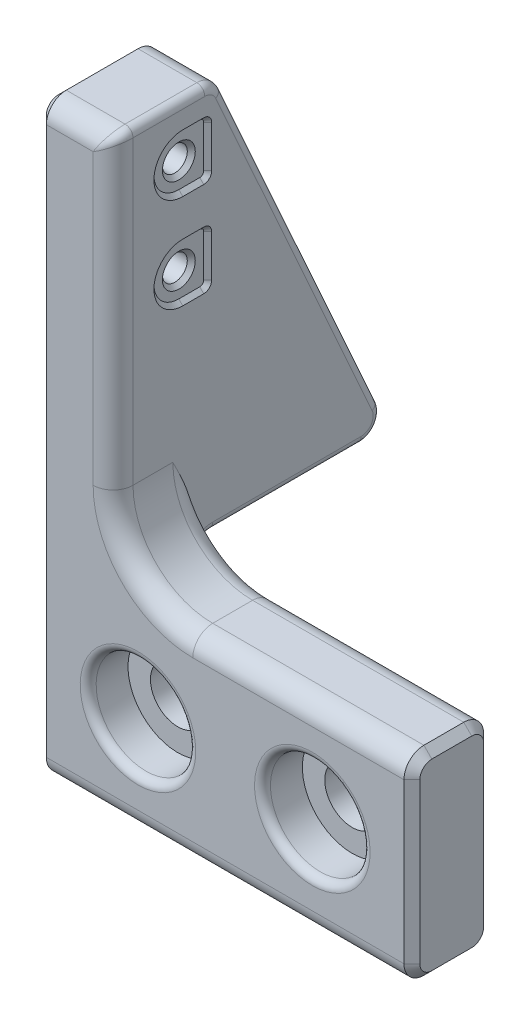
SolidWorks part; units mm, degrees
ref_plane "Front Plane" through (0, 0, 0) normal (0, 0, 1) x (1, 0, 0)
ref_plane "Top Plane" through (0, 0, 0) normal (0, 1, 0) x (1, 0, 0)
ref_plane "Right Plane" through (0, 0, 0) normal (1, 0, 0) x (0, 0, -1)
sketch "Sketch1" plane through (0, 0, 0) normal (1, 0, 0) x (0, 0, -1)
  line L6 (0, 0) -> (0, 20)
  line L7 (0, 20) -> (20, 20)
  line L8 (20, 20) -> (2.5, 59)
  line L9 (2.5, 59) -> (-8, 59)
  line L10 (-8, 59) -> (-8, 0)
  line L11 (-8, 0) -> (0, 0)
  dimension "D1" = 8
  dimension "D2" = 20
  dimension "D3" = 59
  dimension "D4" = 10.5
extrude "Boss-Extrude1" add sketch "Sketch1" against normal blind 7.5 contours L8 L9 L10 L11 L6 L7
sketch "Sketch2" plane through (0, 0, 0) normal (-1, 0, 0) x (0, 0, 1)
  line L0 (8, 59) -> (8, 0) construction
  line L1 (0, 0) -> (8, 0)
  line L2 (0, 0) -> (0, 20)
  line L3 (0, 20) -> (8, 20)
  line L4 (8, 0) -> (8, 20)
  line L5 (0, 20) -> (-20, 20) construction
extrude "Boss-Extrude2" add sketch "Sketch2" against normal blind 30
hole_wizard "CBORE for M5 SHCS1" positions "Sketch3" profile "Sketch4" counterbore size "M5" standard "ANSI Metric" end condition through all
sketch "Sketch3" plane through (0, 0, 8) normal (0, 0, 1) x (1, 0, 0)
  line L0 (30, 10) -> (20, 10) construction
  line L1 (30, 0) -> (30, 20) construction
  line L2 (20, 10) -> (2.5, 10) construction
  line L4 (30, 0) -> (30, 20) construction
  line L5 (-7.5, 59) -> (-7.5, 0) construction
  point P0 (2.5, 10)
  point P2 (20, 10)
  dimension "D1" = 10
  dimension "D2" = 10
sketch "Sketch4" plane through (2.5, 10, 8) normal (1, 0, 0) x (0, -1, 0)
  line L0 (0, 0) -> (0, 28)
  line L1 (0, 28) -> (2.75, 28)
  line L3 (2.75, 28) -> (2.75, 4)
  line L4 (2.75, 4) -> (5, 4)
  line L5 (5, 4) -> (5, 0)
  line L7 (5, 0) -> (0, 0)
  line L11 (0, -6.35) -> (0, 107.95) construction
  dimension "Thru Hole Dia." = 5.5
  dimension "Thru Hole Depth" = 28
  dimension "C'Bore Dia." = 10
  dimension "C'Bore Depth" = 4
sketch "Sketch5" plane through (0, 0, 0) normal (1, 0, 0) x (0, 0, -1)
  line L0 (-1, 44) -> (-1, 53.5) construction
  line L1 (-8, 59) -> (-8, 20) construction
  line L3 (2.5, 59) -> (-8, 59) construction
  circle A0 centre (-1, 53.5) radius 1.25
  circle A1 centre (-1, 44) radius 1.25
  dimension "D1" = 2.5
  dimension "D4" = 5.5
  dimension "D2" = 9.5
  dimension "D3" = 7
extrude "Cut-Extrude1" cut sketch "Sketch5" against normal through all
sketch "Sketch7" plane through (0, 0, 0) normal (1, 0, 0) x (0, 0, -1)
  line L0 (-1, 56) -> (1.5, 56)
  line L1 (1.5, 56) -> (1.5, 51)
  line L2 (1.5, 51) -> (-1, 51)
  line L3 (-1, 46.5) -> (1.5, 46.5)
  line L4 (1.5, 46.5) -> (1.5, 41.5)
  line L5 (1.5, 41.5) -> (-1, 41.5)
  arc A0 (-1, 46.5) -> (-1, 41.5) centre (-1, 44) ccw
  arc A1 (-1, 56) -> (-1, 51) centre (-1, 53.5) ccw
  dimension "D1" = 5
extrude "Cut-Extrude2" cut sketch "Sketch7" against normal blind 0.4
fillet "Fillet5" radius 8 1 edges at (0, 20, 4)
fillet "Fillet1" radius 2 9 edges at (19, 20, 8) (11.25, 0, 8) (11.25, 0, 0) (-3.75, 59, 8) (-3.75, 59, -2.5) (-3.75, 20, -20) (-3.75, 20, 0) (0, 43.5, 8) (2.3431, 22.3431, 8)
fillet "Fillet2" radius 2 2 edges at (19, 20, 0) (2.3431, 22.3431, 0)
chamfer "Chamfer1" distance 0.8 angle 45 22 edges at (30, 19.4142, 7.4142) (30, 10, 8) (30, 0.5858, 7.4142) (30, 0, 4) (30, 0.5858, 0.5858) (30, 10, 0) (30, 19.4142, 0.5858) (30, 20, 4) (-7.5, 44, -0.25) (-7.5, 53.5, -0.25) (-7.5, 0.5858, 0.5858) (-7.5, 10, 0) (-7.5, 19.4142, -0.5858) (-7.5, 20, -9.4552) (-7.5, 20.9132, -18.5894) (-7.5, 40.3188, -10.8826) (-7.5, 58.6789, -2.2922) (-7.5, 59, 2.3973) (-7.5, 58.4142, 7.4142) (-7.5, 29.5, 8) (-7.5, 0.5858, 7.4142) (-7.5, 0, 4)
fillet "Fillet3" radius 0.8 7 edges at (0, 19.4142, -0.5858) (0, 20, -9.4552) (0, 20.9132, -18.5894) (0, 40.3188, -10.8826) (0, 58.6789, -2.2922) (0, 59, 2.3973) (-0.5858, 58.4142, 7.4142)
fillet "Fillet4" radius 0.8 2 edges at (25, 10, 8) (7.5, 10, 8)
fillet "Fillet6" radius 0.4 4 edges at (-0.2, 51, -1.5) (-0.2, 41.5, -1.5) (-0.2, 46.5, -1.5) (-0.2, 56, -1.5)
chamfer "Chamfer2" distance 0.4 angle 45 14 edges at (0, 53.5, 3.5) (0, 44, 3.5) (-0.4, 44, -0.25) (-0.4, 53.5, -0.25) (0, 56, -0.05) (0, 51, -0.05) (0, 46.5, -0.05) (0, 41.5, -0.05) (0, 53.5, -1.5) (0, 44, -1.5) (0, 51.1172, -1.3828) (0, 55.8828, -1.3828) (0, 41.6172, -1.3828) (0, 46.3828, -1.3828)
